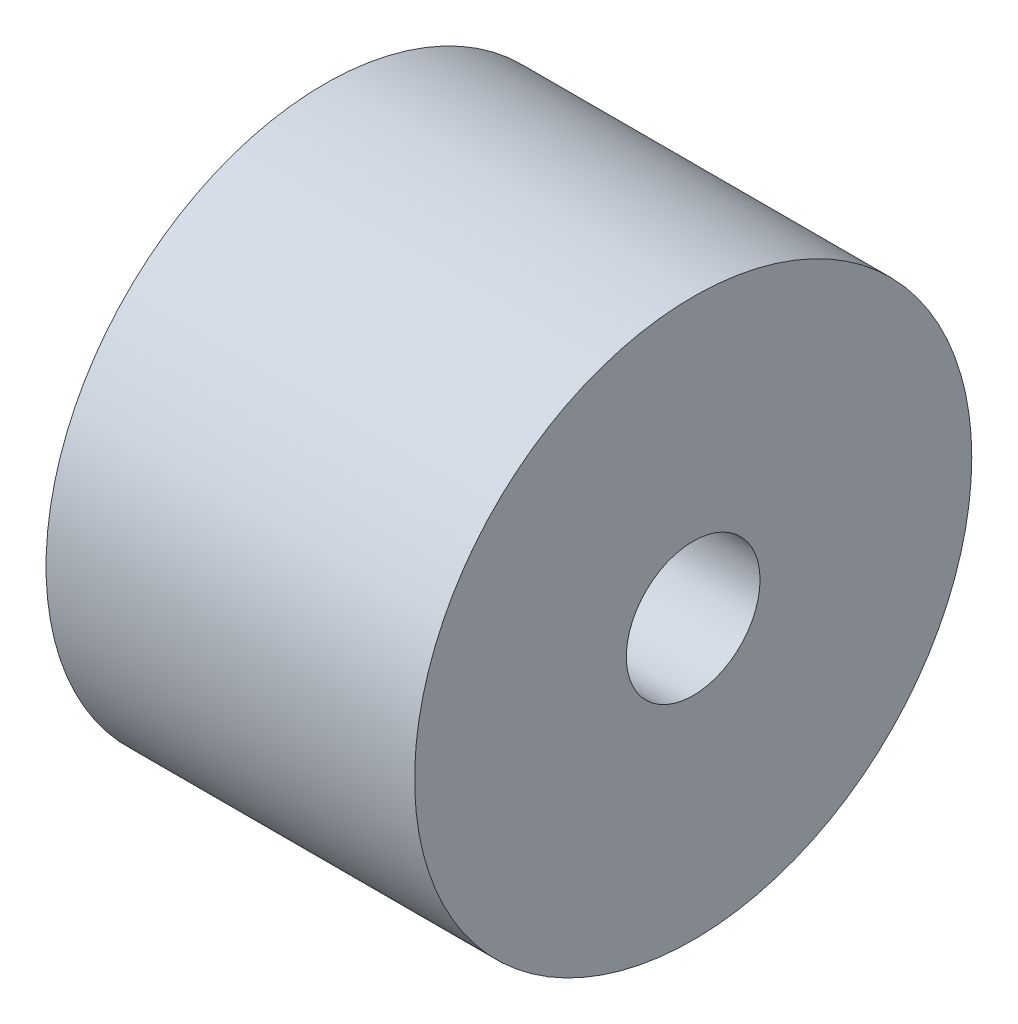
SolidWorks part; units mm, degrees
material "Oak"
ref_plane "Front" through (0, 0, 0) normal (0, 0, 1) x (1, 0, 0)
ref_plane "Top" through (0, 0, 0) normal (0, 1, 0) x (1, 0, 0)
ref_plane "Right" through (0, 0, 0) normal (1, 0, 0) x (0, 0, -1)
ref_axis "side-side" through (80.9, 0, 0) along (-1, 0, 0)
ref_axis "up-down" through (0, 50, 0) along (0, -1, 0)
ref_axis "front-back" through (0, 0, -80.9) along (0, 0, 1)
sketch "Sketch1" plane through (0, 0, 0) normal (0, 0, 1) x (1, 0, 0)
  line L0 (0, 0) -> (-61.4641, 0) construction
  line L2 (0, 7.9375) -> (10.5, 7.9375)
  line L3 (0, 7.9375) -> (0, 1.905)
  line L5 (10.5, 7.9375) -> (10.5, 1.905)
  line L8 (0, 1.905) -> (10.5, 1.905)
  dimension "D1" = 3.81
  dimension "D3" = 15.875
  dimension "D4" = 10.5
revolve "Revolve1" add sketch "Sketch1" angle 360 about L0
